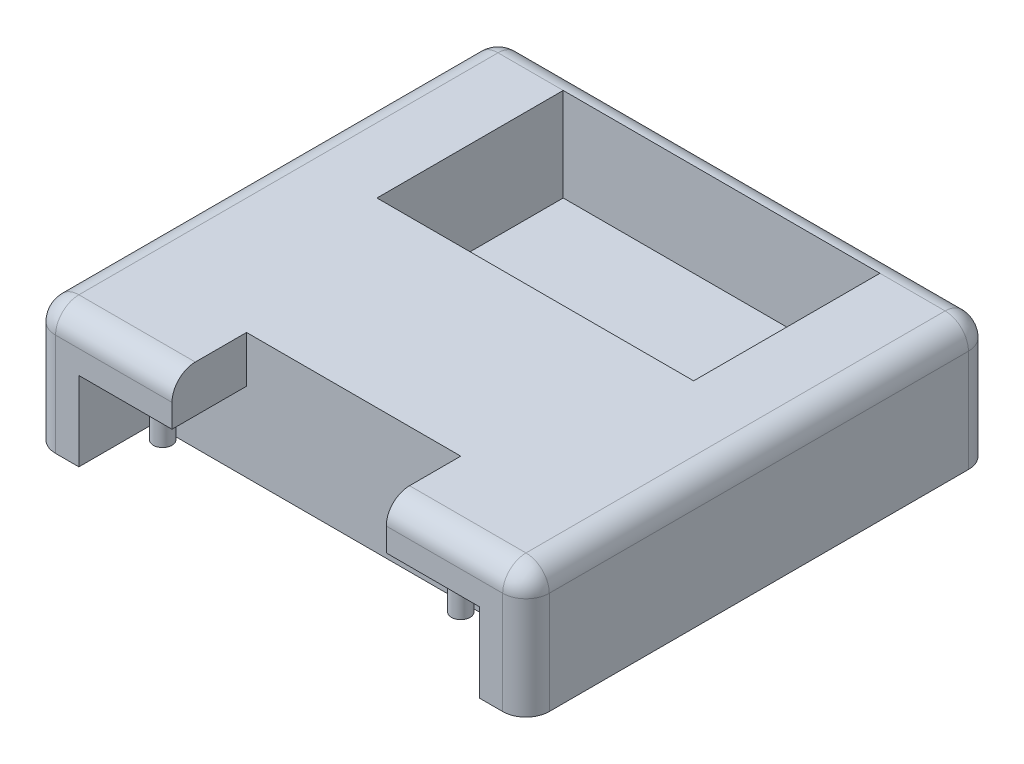
SolidWorks part; units mm, degrees
ref_plane "前视基准面" through (0, 0, 0) normal (0, 0, 1) x (1, 0, 0)
ref_plane "上视基准面" through (0, 0, 0) normal (0, 1, 0) x (1, 0, 0)
ref_plane "右视基准面" through (0, 0, 0) normal (1, 0, 0) x (0, 0, -1)
sketch "草图2" plane through (0, 0, 0) normal (0, 1, 0) x (1, 0, 0)
  line L11 (-53, -50) -> (53, -50)
  line L12 (-53, -50) -> (-53, 50)
  line L13 (-53, 50) -> (53, 50)
  line L14 (53, -50) -> (53, 50)
  line L15 (-53, -50) -> (53, 50) construction
  line L16 (-53, 50) -> (53, -50) construction
  point P0 (0, 0)
  point P3 (0, 0)
  point P6 (0, 0)
  point P8 (-53, 50)
  dimension "D1" = 100
  dimension "D2" = 106
extrude "凸台-拉伸1" add sketch "草图2" along normal blind 10
sketch "草图3" plane through (0, 0, 0) normal (0, -1, 0) x (1, 0, 0)
  line L0 (-53, 50) -> (53, 50) construction
  line L1 (-32, -43) -> (32, -43) construction
  line L2 (-32, -43) -> (-32, 43) construction
  line L3 (-32, 43) -> (32, 43) construction
  line L4 (32, -43) -> (32, 43) construction
  line L5 (-32, -43) -> (32, 43) construction
  line L6 (-32, 43) -> (32, -43) construction
  circle A0 centre (-32, 43) radius 2
  circle A1 centre (32, 43) radius 2
  point P0 (0, 0)
  dimension "D2" = 7
  dimension "D1" = 64
extrude "凸台-拉伸2" add sketch "草图3" along normal blind 10
sketch "草图4" plane through (0, 0, 0) normal (0, -1, 0) x (1, 0, 0)
  line L0 (53, -50) -> (-53, -50) construction
  line L1 (-53, 50) -> (-43, 50)
  line L2 (-53, 50) -> (-53, -50)
  line L3 (-53, -50) -> (-43, -50)
  line L4 (-43, 50) -> (-43, 34)
  line L6 (53, 50) -> (43, 50)
  line L7 (53, 50) -> (53, -50)
  line L8 (53, -50) -> (43, -50)
  line L9 (43, 50) -> (43, 34)
  line L10 (-43, 34) -> (43, 34)
  line L12 (-43, -50) -> (43, -50)
  circle A0 centre (-32, 43) radius 2 construction
  dimension "D3" = 9
  dimension "D1" = 10
  dimension "D2" = 10
extrude "凸台-拉伸3" add sketch "草图4" along normal blind 17
sketch "草图5" plane through (0, 10, 0) normal (0, 1, 0) x (1, 0, 0)
  line L0 (0, 0) -> (0, -50) construction
  line L1 (-53, -50) -> (53, -50) construction
  line L2 (53, 50) -> (-53, 50) construction
  line L3 (-34, 5) -> (34, 5)
  line L4 (-34, 5) -> (-34, 45)
  line L5 (-34, 45) -> (34, 45)
  line L6 (34, 5) -> (34, 45)
  line L7 (-34, 5) -> (34, 45) construction
  line L8 (-34, 45) -> (34, 5) construction
  point P5 (0, 25)
  dimension "D1" = 68
  dimension "D2" = 40
  dimension "D3" = 5
extrude "切除-拉伸1" cut sketch "草图5" against normal blind 20
sketch "草图6" plane through (0, 0, 0) normal (0, -1, 0) x (1, 0, 0)
  line L0 (-43, 50) -> (43, 50) construction
  line L1 (-23, 66) -> (23, 66)
  line L2 (-23, 66) -> (-23, 34)
  line L3 (-23, 34) -> (23, 34)
  line L4 (23, 66) -> (23, 34)
  line L5 (-23, 66) -> (23, 34) construction
  line L6 (-23, 34) -> (23, 66) construction
  line L7 (43, 34) -> (-43, 34) construction
  point P0 (0, 50)
  dimension "D1" = 46
extrude "切除-拉伸2" cut sketch "草图6" against normal blind 20
fillet "圆角1" radius 3 2 edges at (32, 0, 41) (-32, 0, 41)
fillet "圆角2" radius 5 8 edges at (0, 10, -50) (53, 10, 0) (-53, 10, 0) (53, -3.5, -50) (53, -3.5, 50) (-53, -3.5, 50) (-53, -3.5, -50) (-38, 10, 50)
